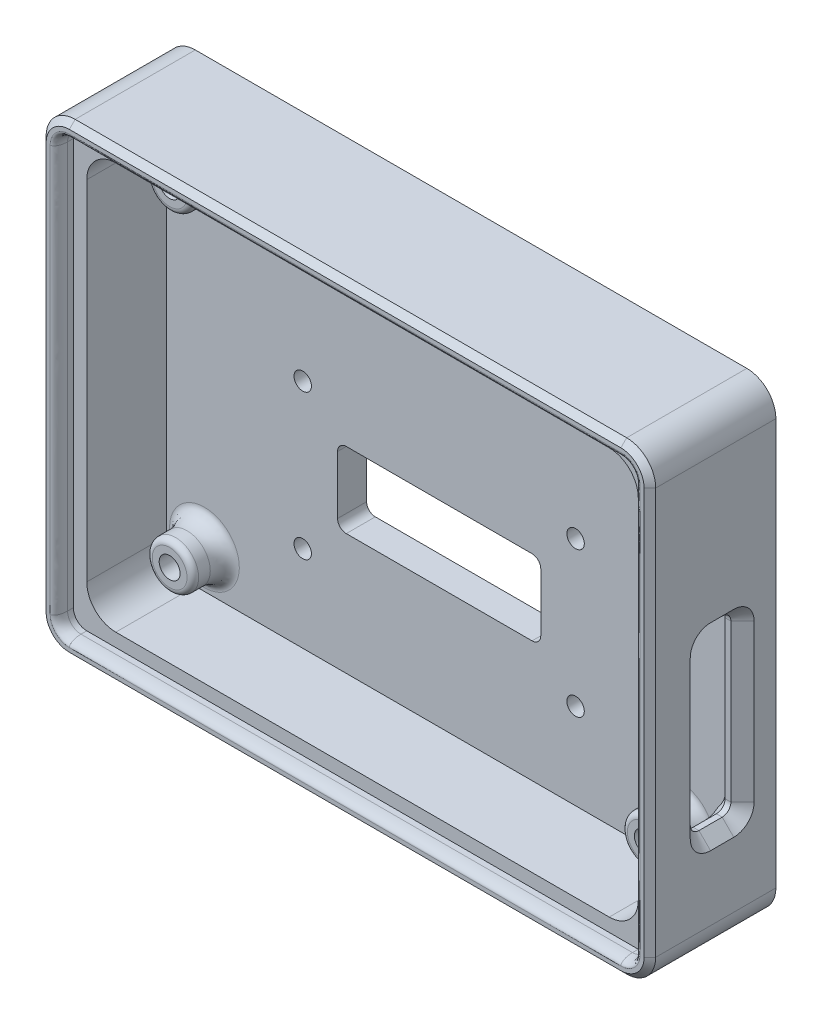
SolidWorks part; units mm, degrees
material "ABS"
ref_plane "Płaszczyzna przednia" through (0, 0, 0) normal (0, 0, 1) x (1, 0, 0)
ref_plane "Płaszczyzna górna" through (0, 0, 0) normal (0, 1, 0) x (1, 0, 0)
ref_plane "Płaszczyzna prawa" through (0, 0, 0) normal (1, 0, 0) x (0, 0, -1)
sketch "Szkic1" plane through (0, 0, 0) normal (0, 0, 1) x (1, 0, 0)
  line L1 (-52.5, 40) -> (52.5, 40)
  line L2 (-52.5, 40) -> (-52.5, -40)
  line L3 (-52.5, -40) -> (52.5, -40)
  line L4 (52.5, 40) -> (52.5, -40)
  line L5 (-52.5, 40) -> (52.5, -40) construction
  line L6 (-52.5, -40) -> (52.5, 40) construction
  point P1 (0, 0)
  dimension "D1" = 105
  dimension "D2" = 80
extrude "Dodanie-wyciągnięcie1" add sketch "Szkic1" along normal blind 21.7
shell "Skorupa2" thickness 5 removed face at (0, 0, 21.7)
sketch "Szkic2" plane through (0, 0, 5) normal (0, 0, 1) x (1, 0, 0)
  line L1 (-40.925, 28.425) -> (40.925, 28.425) construction
  line L2 (-40.925, 28.425) -> (-40.925, -28.425) construction
  line L3 (-40.925, -28.425) -> (40.925, -28.425) construction
  line L4 (40.925, 28.425) -> (40.925, -28.425) construction
  line L5 (-40.925, 28.425) -> (40.925, -28.425) construction
  line L6 (-40.925, -28.425) -> (40.925, 28.425) construction
  point P0 (0, 0)
  dimension "D1" = 81.85
  dimension "D2" = 56.85
hole_wizard "Otwór gwintowany M3x0.51" positions "Szkic3" profile "Szkic4" hole size "M3x0.5" standard "Ansi Metric"
sketch "Szkic3" plane through (0, 0, 5) normal (0, 0, 1) x (1, 0, 0)
  point P0 (-40.925, 28.425)
  point P3 (40.925, 28.425)
  point P6 (40.925, -28.425)
  point P9 (-40.925, -28.425)
sketch "Szkic4" plane through (-40.925, 28.425, 5) normal (1, 0, 0) x (0, -1, 0)
  line L0 (0, 0) -> (0, 6.7511)
  line L1 (0, 6.7511) -> (1.25, 6)
  line L2 (1.25, 6) -> (1.25, 0)
  line L5 (1.25, 0) -> (0, 0)
  line L10 (0, 6.7511) -> (-1.25, 6) construction
  line L11 (0, -6.35) -> (0, 107.95) construction
  dimension "Średnica otworu" = 2.5
  dimension "Głębokość otworu" = 6
  dimension "Kąt wiertła" = 118
sketch "Szkic7" plane through (0, 0, 5) normal (0, 0, 1) x (1, 0, 0)
  line L1 (-18, -1.145) -> (17, -1.145)
  line L2 (-18, -1.145) -> (-18, -14.145)
  line L3 (-18, -14.145) -> (17, -14.145)
  line L4 (17, -1.145) -> (17, -14.145)
  line L5 (-18, -1.145) -> (17, -14.145) construction
  line L6 (-18, -14.145) -> (17, -1.145) construction
  line L8 (14.89, -10.96) -> (-15.89, -10.96) construction
  line L9 (-15.89, -10.96) -> (-15.89, -4.33) construction
  point P0 (0, -7.4593)
  point P5 (-0.5, -14.145)
  point P9 (-0.5, -10.96)
  point P10 (-18, -7.645)
  point P13 (-15.89, -7.645)
  dimension "D1" = 35
  dimension "D2" = 13
extrude "Wytnij-wyciągnięcie1" cut sketch "Szkic7" against normal through all
fillet "Zaokrąglenie1" radius 5 8 edges at (-52.5, 40, 10.85) (-52.5, -40, 10.85) (52.5, -40, 10.85) (52.5, 40, 10.85) (47.5, -35, 13.35) (-47.5, -35, 13.35) (-47.5, 35, 13.35) (47.5, 35, 13.35)
sketch "Szkic8" plane through (52.5, 0, 0) normal (1, 0, 0) x (0, 0, -1)
  line L0 (-7.5, 6.93) -> (-7.5, -20.57) construction
  line L1 (-11.25, -21.82) -> (-7.25, -21.82)
  line L2 (-12.75, -20.32) -> (-12.75, 6.68)
  line L3 (-11.25, 8.18) -> (-7.25, 8.18)
  line L4 (-5.75, -20.32) -> (-5.75, 6.68)
  line L5 (-7.5, 6.93) -> (-7.5, -20.57)
  line L8 (-7.5, -20.57) -> (-11, -20.57) construction
  line L9 (-7.5, -20.57) -> (-11, -20.57)
  arc A0 (-11.25, -21.82) -> (-12.75, -20.32) centre (-11.25, -20.32) cw
  arc A1 (-7.25, -21.82) -> (-5.75, -20.32) centre (-7.25, -20.32) ccw
  arc A2 (-7.25, 8.18) -> (-5.75, 6.68) centre (-7.25, 6.68) cw
  arc A3 (-12.75, 6.68) -> (-11.25, 8.18) centre (-11.25, 6.68) cw
  point P4 (-9.25, -21.82)
  point P5 (-9.25, -20.57)
  point P12 (-5.75, -21.82)
  point P15 (-5.75, 8.18)
  point P18 (-12.75, 8.18)
  point P19 (-5.75, -6.82)
  point P20 (-7.5, -6.82)
  dimension "D5" = 1.5
  dimension "D1" = 7
  dimension "D2" = 30
extrude "Wytnij-wyciągnięcie2" cut sketch "Szkic8" against normal up to surface (5 mm away) contours L2 A3 L3 A2 L4 A1 L1 A0 up to face at (47.5, 0, 13.35)
sketch "Szkic13" plane through (0, 0, 21.7) normal (0, 0, 1) x (1, 0, 0)
  line L0 (47.5, 37.3) -> (-47.5, 37.3)
  line L1 (-49.8, 35) -> (-49.8, -35)
  line L2 (-47.5, -37.3) -> (47.5, -37.3)
  line L3 (49.8, -35) -> (49.8, 35)
  line L4 (-49.6, 35) -> (-49.6, -35) construction
  line L5 (-47.5, -37.1) -> (47.5, -37.1) construction
  line L6 (49.6, -35) -> (49.6, 35) construction
  line L7 (47.5, 37.1) -> (-47.5, 37.1) construction
  line L8 (47.5, 40.1) -> (-47.5, 40.1)
  line L9 (47.5, 40.1) -> (-47.5, 40.1)
  line L10 (-52.6, 35) -> (-52.6, -35)
  line L11 (-52.6, 35) -> (-52.6, -35)
  line L12 (-47.5, -40.1) -> (47.5, -40.1)
  line L13 (-47.5, -40.1) -> (47.5, -40.1)
  line L14 (52.6, -35) -> (52.6, 35)
  line L15 (52.6, -35) -> (52.6, 35)
  arc A0 (-47.5, 37.3) -> (-49.8, 35) centre (-47.5, 35) ccw
  arc A1 (-49.8, -35) -> (-47.5, -37.3) centre (-47.5, -35) ccw
  arc A2 (47.5, -37.3) -> (49.8, -35) centre (47.5, -35) ccw
  arc A3 (49.8, 35) -> (47.5, 37.3) centre (47.5, 35) ccw
  arc A4 (-49.6, -35) -> (-47.5, -37.1) centre (-47.5, -35) ccw construction
  arc A5 (47.5, -37.1) -> (49.6, -35) centre (47.5, -35) ccw construction
  arc A6 (49.6, 35) -> (47.5, 37.1) centre (47.5, 35) ccw construction
  arc A7 (-47.5, 37.1) -> (-49.6, 35) centre (-47.5, 35) ccw construction
  arc A8 (-47.5, 40.1) -> (-52.6, 35) centre (-47.5, 35) ccw
  arc A9 (-47.5, 40.1) -> (-52.6, 35) centre (-47.5, 35) ccw
  arc A10 (-52.6, -35) -> (-47.5, -40.1) centre (-47.5, -35) ccw
  arc A11 (-52.6, -35) -> (-47.5, -40.1) centre (-47.5, -35) ccw
  arc A12 (47.5, -40.1) -> (52.6, -35) centre (47.5, -35) ccw
  arc A13 (47.5, -40.1) -> (52.6, -35) centre (47.5, -35) ccw
  arc A14 (52.6, 35) -> (47.5, 40.1) centre (47.5, 35) ccw
  arc A15 (52.6, 35) -> (47.5, 40.1) centre (47.5, 35) ccw
  line M9 (47.5, 30) -> (47.5, -30)
  arc M10 (47.5, -30) -> (42.5, -35) centre (42.5, -30) cw
  line M11 (42.5, -35) -> (-42.5, -35)
  arc M12 (-42.5, -35) -> (-47.5, -30) centre (-42.5, -30) cw
  line M13 (-47.5, -30) -> (-47.5, 30)
  arc M14 (-47.5, 30) -> (-42.5, 35) centre (-42.5, 30) cw
  line M15 (-42.5, 35) -> (42.5, 35)
  arc M16 (42.5, 35) -> (47.5, 30) centre (42.5, 30) cw
  dimension "D2" = 95
  dimension "D3" = 0.2
  dimension "D1" = 0.1
extrude "Wytnij-wyciągnięcie5" cut sketch "Szkic13" against normal blind 3 contours L7 A7 L4 A4 L5 A5 L6 A6 M16 M9 M10 M11 M12 M13 M14 M15 region at (48.2464, 35.7464, 21.7)
chamfer "Sfazowanie1" distance 2 angle 45 16 edges at (52.5, 8.18, 9.25) (52.5, 7.7407, 6.1893) (52.5, 7.7407, 12.3107) (52.5, -6.82, 12.75) (52.5, -21.3807, 12.3107) (52.5, -21.82, 9.25) (52.5, -21.3807, 6.1893) (52.5, -6.82, 5.75) (47.5, -6.82, 5.75) (47.5, -21.3807, 6.1893) (47.5, 7.7407, 6.1893) (47.5, -21.82, 9.25) (47.5, 8.18, 9.25) (47.5, -21.3807, 12.3107) (47.5, 7.7407, 12.3107) (47.5, -6.82, 12.75)
fillet "Zaokrąglenie2" radius 1.5 4 edges at (-18, -14.145, 2.5) (17, -14.145, 2.5) (17, -1.145, 2.5) (-18, -1.145, 2.5)
sketch "Szkic14" plane through (0, 0, 5) normal (0, 0, 1) x (1, 0, 0)
  circle A0 centre (-40.925, 28.425) radius 4
  circle A1 centre (40.925, 28.425) radius 4
  circle A2 centre (-40.925, -28.425) radius 4
  circle A3 centre (40.925, -28.425) radius 4
  circle A4 centre (40.925, -28.425) radius 1.25 construction
  circle A5 centre (-40.925, -28.425) radius 1.25 construction
  circle A6 centre (40.925, 28.425) radius 1.25 construction
  circle A7 centre (-40.925, 28.425) radius 1.25 construction
  circle A8 centre (40.925, -28.425) radius 1.25
  circle A9 centre (-40.925, -28.425) radius 1.25
  circle A10 centre (40.925, 28.425) radius 1.25
  circle A11 centre (-40.925, 28.425) radius 1.25
  dimension "D1" = 8
extrude "Dodanie-wyciągnięcie2" add sketch "Szkic14" along normal blind 6
fillet "Zaokrąglenie3" radius 1 4 edges at (44.925, -28.425, 11) (-36.925, -28.425, 11) (44.925, 28.425, 11) (-36.925, 28.425, 11)
fillet "Zaokrąglenie4" radius 1 8 edges at (49.8, 0, 21.7) (49.1263, 36.6263, 21.7) (49.1263, -36.6263, 21.7) (0, 37.3, 21.7) (0, -37.3, 21.7) (-49.1263, 36.6263, 21.7) (-49.1263, -36.6263, 21.7) (-49.8, 0, 21.7) second distance 2 first distance on face at (0, 0, 21.7)
chamfer "Sfazowanie2" distance 1 angle 45 8 edges at (-52.5, 0, 21.7) (-51.0355, -38.5355, 21.7) (-51.0355, 38.5355, 21.7) (0, -40, 21.7) (0, 40, 21.7) (51.0355, -38.5355, 21.7) (51.0355, 38.5355, 21.7) (52.5, 0, 21.7)
sketch "Szkic16" plane through (0, 0, 0) normal (0, 0, -1) x (-1, 0, 0)
  circle A0 centre (40.925, -28.425) radius 1.8
  circle A1 centre (-40.925, -28.425) radius 1.8
  circle A2 centre (-40.925, 28.425) radius 1.8
  circle A3 centre (40.925, 28.425) radius 1.8
extrude "Wytnij-wyciągnięcie6" cut sketch "Szkic16" against normal through all
sketch "Szkic17" plane through (0, 0, 0) normal (0, 0, -1) x (-1, 0, 0)
  circle A0 centre (40.925, -28.425) radius 3.5
  circle A1 centre (-40.925, -28.425) radius 3.8
  circle A2 centre (-40.925, 28.425) radius 3.8
  circle A3 centre (40.925, 28.425) radius 3.5
extrude "Wytnij-wyciągnięcie7" cut sketch "Szkic17" against normal blind 3.5
fillet "Zaokrąglenie5" radius 2 4 edges at (44.925, 28.425, 5) (-36.925, 28.425, 5) (-36.925, -28.425, 5) (44.925, -28.425, 5) second distance 3 first distance on face at (-36.925, -28.425, 5)
sketch "Szkic20" plane through (0, 0, 5) normal (0, 0, 1) x (1, 0, 0)
  line L0 (-0.5, -14.145) -> (-0.5, -1.145) construction
  line L1 (-16.5, -14.145) -> (15.5, -14.145) construction
  line L2 (15.5, -1.145) -> (-16.5, -1.145) construction
  line L3 (-0.5, -7.645) -> (-24, -7.645) construction
  line L4 (-24, -7.645) -> (-24, 4.855) construction
  line L5 (-18, -2.645) -> (-18, -12.645) construction
  circle A0 centre (-24, 4.855) radius 1.5
  circle A1 centre (-24, -20.145) radius 1.5
  circle A2 centre (23, -20.145) radius 1.5
  circle A3 centre (23, 4.855) radius 1.5
  dimension "D1" = 6
  dimension "D2" = 6
extrude "Wytnij-wyciągnięcie8" cut sketch "Szkic20" against normal through all
